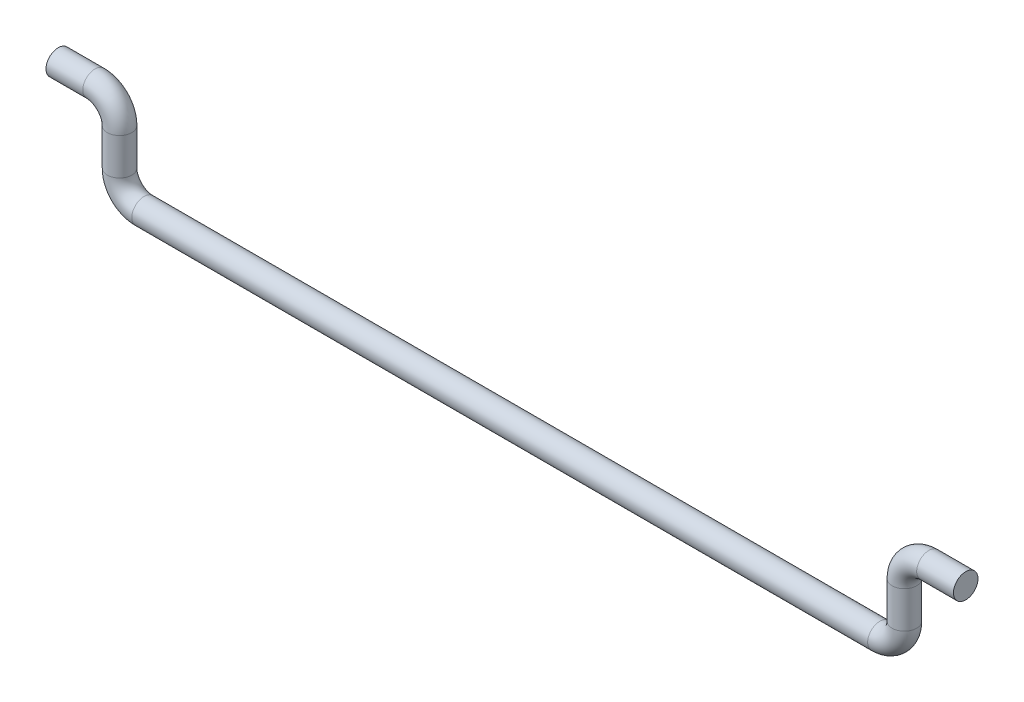
SolidWorks part; units mm, degrees
material "Cast Alloy Steel"
ref_plane "Front Plane" through (0, 0, 0) normal (0, 0, 1) x (1, 0, 0)
ref_plane "Top Plane" through (0, 0, 0) normal (0, 1, 0) x (1, 0, 0)
ref_plane "Right Plane" through (0, 0, 0) normal (1, 0, 0) x (0, 0, -1)
sketch "Sketch1" plane through (0, 0, 0) normal (0, 0, 1) x (1, 0, 0)
  line L0 (0, 0) -> (-60, 0)
  line L1 (-62, 2) -> (-62, 5)
  line L2 (-30, 0) -> (-30, 16.7563) construction
  line L3 (-64, 7) -> (-67, 7)
  line L4 (2, 2) -> (2, 5)
  line L5 (4, 7) -> (7, 7)
  arc A0 (-60, 0) -> (-62, 2) centre (-60, 2) cw
  arc A1 (-62, 5) -> (-64, 7) centre (-64, 5) ccw
  arc A2 (0, 0) -> (2, 2) centre (0, 2) ccw
  arc A3 (2, 5) -> (4, 7) centre (4, 5) cw
  dimension "D2" = 2
  dimension "D1" = 60
  dimension "D3" = 3
  dimension "D4" = 3
ref_plane "Plane1" through (7, 0, 0) normal (1, 0, 0) x (0, 0, -1)
sketch "Sketch3" plane through (7, 0, 0) normal (1, 0, 0) x (0, 0, -1)
  circle A0 centre (0.4304, 7) radius 1
  dimension "D1" = 2
sweep "Sweep2" add profiles "Sketch3" path "Sketch1"
ref_plane "Plane2" through (0, 2, 0) normal (0, 1, 0) x (-1, 0, 0)
sketch "Sketch4" plane through (0, 2, 0) normal (0, 1, 0) x (-1, 0, 0)
  point P0 (62, -0.4304)
